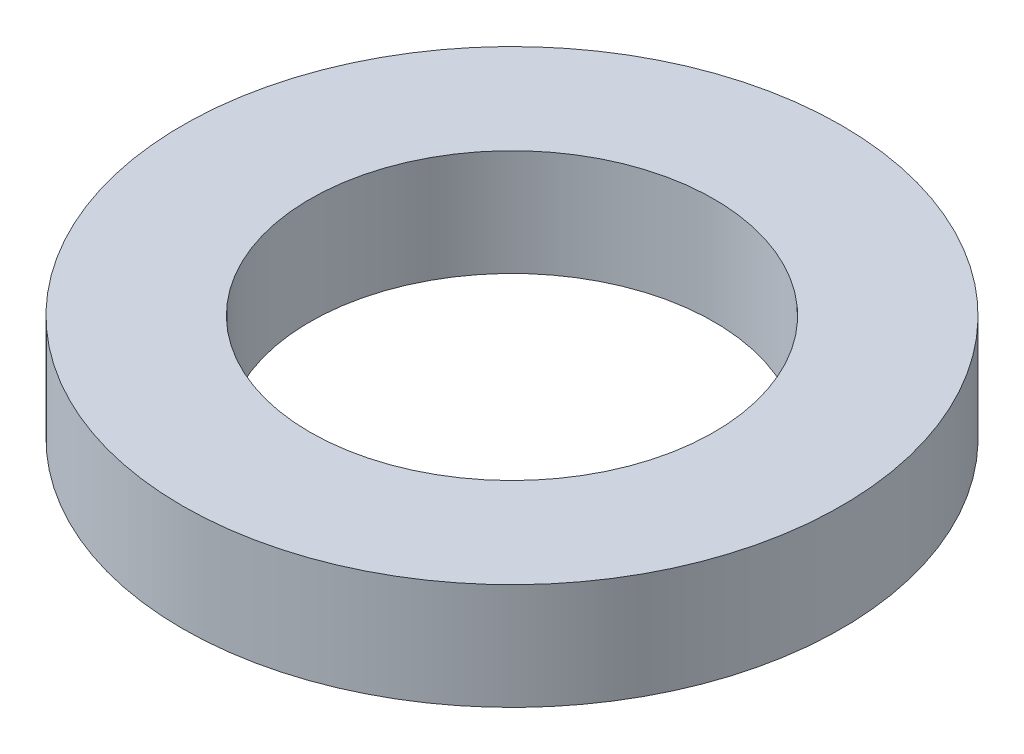
SolidWorks part; units mm, degrees
ref_plane "Front Plane" through (0, 0, 0) normal (0, 0, 1) x (1, 0, 0)
ref_plane "Top Plane" through (0, 0, 0) normal (0, 1, 0) x (1, 0, 0)
ref_plane "Right Plane" through (0, 0, 0) normal (1, 0, 0) x (0, 0, -1)
sketch "Sketch1" plane through (0, 0, 0) normal (0, 1, 0) x (1, 0, 0)
  circle A0 centre (0, 0) radius 77.5
  dimension "FLANGE_OD" = 155
extrude "Boss-Extrude1" add sketch "Sketch1" along normal blind 25
sketch "Sketch2" plane through (0, 0, 0) normal (0, 1, 0) x (1, 0, 0)
  circle A0 centre (0, 0) radius 47.5
  dimension "BORE_D" = 95
extrude "Cut-Extrude1" cut sketch "Sketch2" along normal through all
sketch "Sketch3" plane through (0, 25, 0) normal (0, 1, 0) x (1, 0, 0)
  circle A0 centre (0, 0) radius 30.1876 construction
  circle A1 centre (-30.1876, 0) radius 3.3913
  dimension "BOLT_D" = 6.7827
  dimension "BOLT_PCD" = 60.3752
extrude "Cut-Extrude2" cut sketch "Sketch3" against normal blind 19.9521 rebuild error yes
pattern_circular "CirPattern1" count 6 over 360 rebuild error yes
